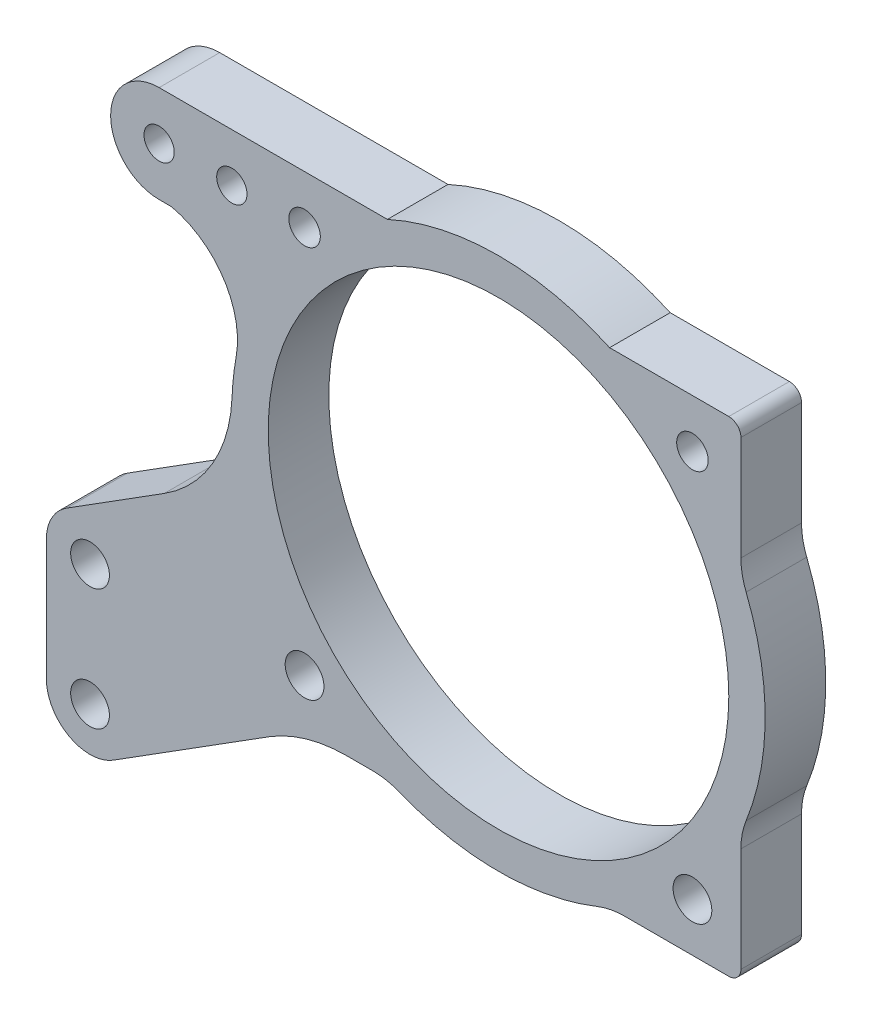
SolidWorks part; units mm, degrees
material "ABS"
ref_plane "Front Plane" through (0, 0, 0) normal (0, 0, 1) x (1, 0, 0)
ref_plane "Top Plane" through (0, 0, 0) normal (0, 1, 0) x (1, 0, 0)
ref_plane "Right Plane" through (0, 0, 0) normal (1, 0, 0) x (0, 0, -1)
sketch "Sketch1" plane through (0, 0, 0) normal (0, 0, 1) x (1, 0, 0)
  line L0 (-37.3, -16.9) -> (-37.3, -26.9)
  line L1 (-20, 20) -> (-9.1652, 20) construction
  line L2 (9.1652, 20) -> (20, 20) construction
  line L3 (-16, -20) -> (-9.1652, -20)
  line L4 (20, 20) -> (20, 9.1652)
  line L5 (-20, 20) -> (20, -20) construction
  line L6 (-20, -20) -> (20, 20) construction
  line L7 (-31.7805, -29.9456) -> (-16, -20)
  line L8 (-35.6195, -13.8544) -> (-21.4429, -4.9197)
  line L9 (-9.1652, 20) -> (-20, 20)
  line L10 (0, 25) -> (0, 0) construction
  line L11 (-20, 20) -> (-20, 9.1652)
  line L13 (20, -9.1652) -> (20, -20)
  line L14 (9.1652, -20) -> (20, -20)
  line L15 (20, 20) -> (9.1652, 20)
  circle A0 centre (0, 0) radius 19
  circle A1 centre (-33.7, -16.9) radius 1.6
  circle A2 centre (-33.7, -26.9) radius 1.6
  circle A3 centre (-16, 16) radius 1.3
  circle A4 centre (16, 16) radius 1.3
  circle A5 centre (16, -16) radius 1.6
  circle A6 centre (-16, -16) radius 1.6
  arc A7 (-35.6195, -13.8544) -> (-37.3, -16.9) centre (-33.7, -16.9) ccw
  arc A8 (-37.3, -26.9) -> (-31.7805, -29.9456) centre (-33.7, -26.9) ccw
  arc A10 (-9.1652, 20) -> (9.1652, 20) centre (0, 0) cw
  arc A17 (20, 9.1652) -> (20, -9.1652) centre (0, 0) cw
  arc A18 (-21.4429, -4.9197) -> (-20, 9.1652) centre (0, 0) cw
  arc A19 (9.1652, -20) -> (-9.1652, -20) centre (0, 0) cw
  point P43 (0, 19)
  dimension "D4" = 38
  dimension "D5" = 2.6
  dimension "D8" = 3.2
  dimension "D9" = 2
  dimension "D11" = 3.2
  dimension "D12" = 3
  dimension "D10" = 3.2
  dimension "D1" = 10
  dimension "D2" = 33.7
  dimension "D3" = 40
  dimension "D6" = 32
  dimension "D7" = 16.9
  dimension "D14" = 40
extrude "Boss-Extrude1" add sketch "Sketch1" along normal blind 5
fillet "Fillet1" radius 12 1 edges at (-21.4429, -4.9197, 2.5)
fillet "Fillet3" radius 12 1 edges at (-16, -20, 2.5)
fillet "Fillet4" radius 1 2 edges at (20, -20, 2.5) (20, 20, 2.5)
fillet "Fillet5" radius 6 4 edges at (20, 9.1652, 2.5) (20, -9.1652, 2.5) (-9.1652, -20, 2.5) (9.1652, -20, 2.5)
sketch "Sketch6" plane through (0, 0, 0) normal (0, 0, -1) x (-1, 0, 0)
  line L0 (22, 20) -> (20, 20)
  line L1 (20, 20) -> (20, 12)
  line L2 (20, 20) -> (20, 9.1652) construction
  line L3 (20, 12) -> (22, 12)
  line L4 (28, 20) -> (22, 20)
  line L5 (28, 12) -> (22, 12)
  line L6 (9.1652, 20) -> (20, 20) construction
  circle A0 centre (22, 16) radius 1.25
  circle A1 centre (28, 16) radius 1.25
  circle A2 centre (16, 16) radius 1.3 construction
  arc A3 (28, 12) -> (28, 20) centre (28, 16) ccw
  dimension "D1" = 2.5
  dimension "D2" = 2.5
  dimension "D3" = 0
  dimension "D4" = 6
  dimension "D5" = 6
extrude "Boss-Extrude3" add sketch "Sketch6" against normal blind 5
fillet "Fillet6" radius 10 1 edges at (-20, 12, 2.5)
fillet "Fillet8" radius 7 1 edges at (-20, 9.1652, 2.5)
